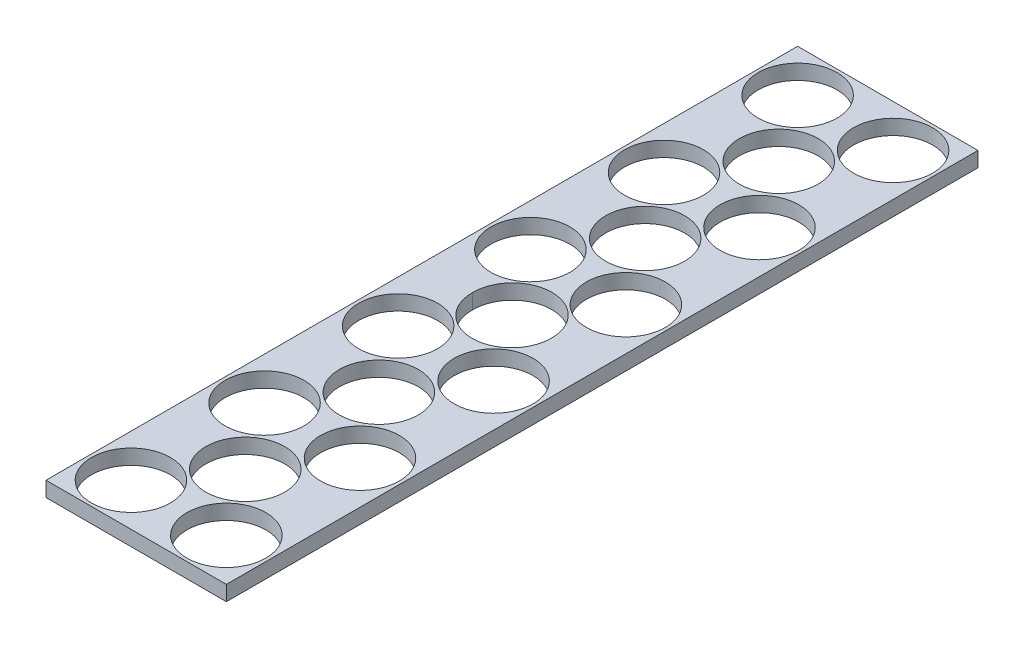
SolidWorks part; units mm, degrees
other "Camera1"
material "PE High Density"
ref_plane "Front Plane" through (0, 0, 0) normal (0, 0, 1) x (1, 0, 0)
ref_plane "Top Plane" through (0, 0, 0) normal (0, 1, 0) x (1, 0, 0)
ref_plane "Right Plane" through (0, 0, 0) normal (1, 0, 0) x (0, 0, -1)
sketch "Sketch1" plane through (0, 0, 0) normal (0, 0, 1) x (1, 0, 0)
  line L1 (76.2, 6.35) -> (-76.2, 6.35)
  line L2 (76.2, 6.35) -> (76.2, -6.35)
  line L3 (76.2, -6.35) -> (-76.2, -6.35)
  line L4 (-76.2, 6.35) -> (-76.2, -6.35)
  line L5 (76.2, 6.35) -> (-76.2, -6.35) construction
  line L6 (76.2, -6.35) -> (-76.2, 6.35) construction
  point P0 (0, 0)
  dimension "width" = 152.4
  dimension "D2" = 12.7
extrude "Boss-Extrude1" add sketch "Sketch1" against normal mid plane 635
sketch "Sketch2" plane through (0, 6.35, 0) normal (0, 1, 0) x (1, 0, 0)
  line L2 (0, -225.3658) -> (-40.3225, -281.6225) construction
  line L3 (73.66, -281.6225) -> (76.2, -281.6225) construction
  line L5 (0, -225.3658) -> (40.3225, -281.6225) construction
  line L6 (-40.3225, -281.6225) -> (-73.66, -281.6225) construction
  line L7 (-73.66, -281.6225) -> (-76.2, -281.6225) construction
  line L8 (-76.2, 317.5) -> (-76.2, -317.5) construction
  line L9 (76.2, 317.5) -> (76.2, -317.5) construction
  line L10 (-19.4214, -252.4619) -> (-20.9011, -254.5264) construction
  line L11 (-40.3225, -314.96) -> (-40.3225, -317.5) construction
  line L12 (76.2, -317.5) -> (-76.2, -317.5) construction
  circle A0 centre (-40.3225, -281.6225) radius 33.3375
  circle A1 centre (0, -225.3658) radius 33.3375
  circle A2 centre (40.3225, -281.6225) radius 33.3375
  dimension "CircleDiameter" = 66.675
  dimension "D4" = 2.54
  dimension "EdgeDistance" = 2.54
extrude "Cut-Extrude1" cut sketch "Sketch2" against normal up to next
pattern_linear "LPattern1" count 3 spacing 112.8712 along (0, 0, -1) of "Cut-Extrude1"
mirror "Mirror1" about plane through (0, 0, 0) normal (0, 0, 1) of "LPattern1"
